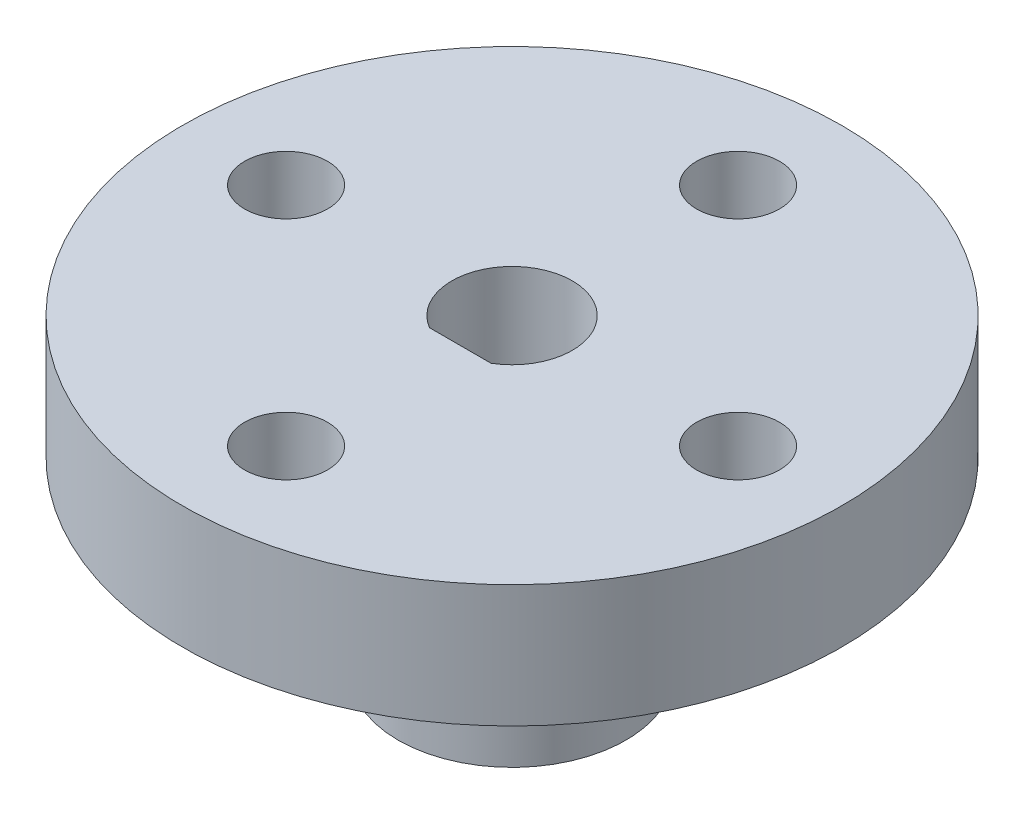
SolidWorks part; units mm, degrees
ref_plane "Front Plane" through (0, 0, 0) normal (0, 0, 1) x (1, 0, 0)
ref_plane "Top Plane" through (0, 0, 0) normal (0, 1, 0) x (1, 0, 0)
ref_plane "Right Plane" through (0, 0, 0) normal (1, 0, 0) x (0, 0, -1)
sketch "Sketch1" plane through (0, 0, 0) normal (0, 1, 0) x (1, 0, 0)
  circle A0 centre (0, 0) radius 3.05
  circle A1 centre (0, 0) radius 6.05
  dimension "D1" = 6.1
  dimension "D2" = 3
extrude "Boss-Extrude1" add sketch "Sketch1" along normal blind 10
sketch "Sketch2" plane through (0, 10, 0) normal (0, 1, 0) x (1, 0, 0)
  circle A0 centre (0, 0) radius 17.5
  dimension "D1" = 35
extrude "Boss-Extrude2" add sketch "Sketch2" along normal blind 6.5
sketch "Sketch3" plane through (0, 10, 0) normal (0, -1, 0) x (1, 0, 0)
  circle A0 centre (12, 0) radius 2.2
  circle A1 centre (0, -12) radius 2.2
  circle A2 centre (-12, 0) radius 2.2
  circle A3 centre (0, 12) radius 2.2
  point P11 (0, 0)
  dimension "D1" = 4.4
  dimension "D3" = 12
  dimension "D2" = 4
extrude "Cut-Extrude1" cut sketch "Sketch3" against normal up to next
sketch "Sketch4" plane through (0, 0, 0) normal (0, 0, 1) x (1, 0, 0)
  circle A0 centre (0, 4.9164) radius 1.5
  dimension "D1" = 3
extrude "Cut-Extrude2" cut sketch "Sketch4" against normal through all both and the other way through all
sketch "Sketch6" plane through (0, 10, 0) normal (0, -1, 0) x (-1, 0, 0)
  circle A0 centre (0, 0) radius 3.2
  dimension "D1" = 6.4
extrude "Cut-Extrude3" cut sketch "Sketch6" against normal up to next and the other way up to next
sketch "Sketch7" plane through (0, 0, 0) normal (0, -1, 0) x (1, 0, 0)
  line L1 (-1.6363, 2.75) -> (1.6363, 2.75)
  circle A2 centre (0, 0) radius 3.2 construction
  arc A3 (-1.6363, 2.75) -> (1.6363, 2.75) centre (0, 0) cw
  point P5 (0, 3.2)
  dimension "D1" = 0.45
extrude "Boss-Extrude3" add sketch "Sketch7" against normal up to surface (16.5 mm away) up to face at (0, 16.5, 3.2)
